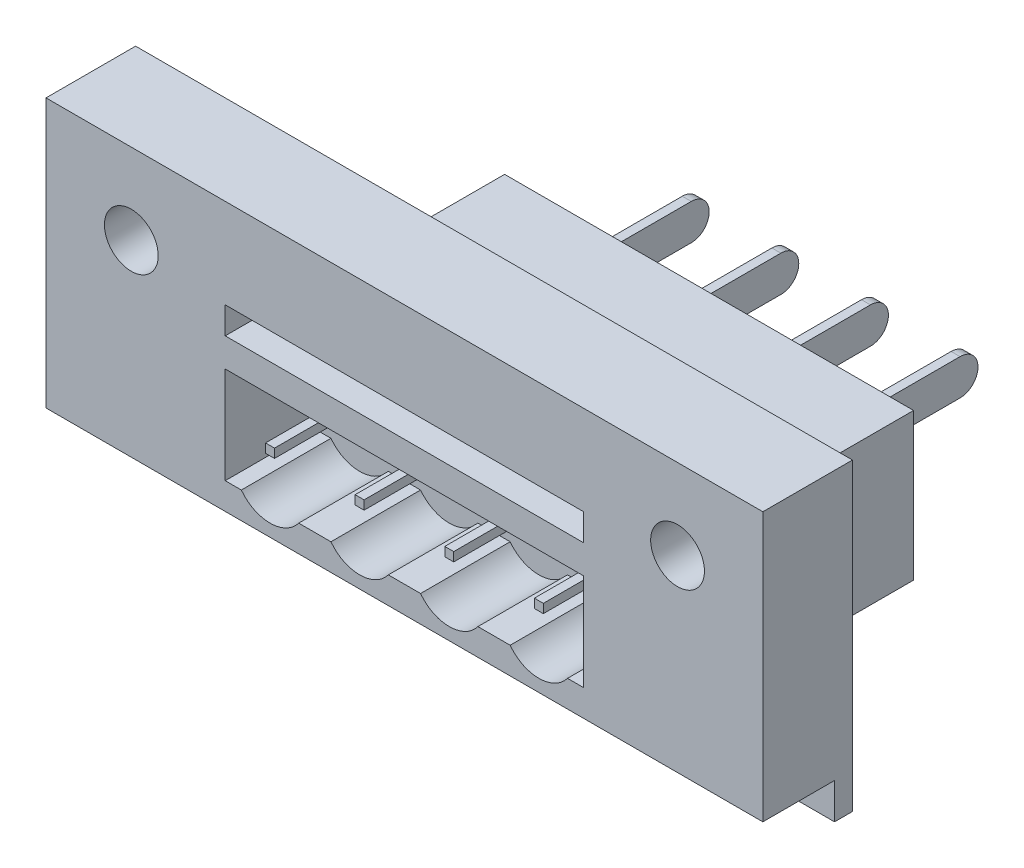
SolidWorks part; units mm, degrees
ref_plane "Front Plane" through (0, 0, 0) normal (0, 0, 1) x (1, 0, 0)
ref_plane "Top Plane" through (0, 0, 0) normal (0, 1, 0) x (1, 0, 0)
ref_plane "Right Plane" through (0, 0, 0) normal (1, 0, 0) x (0, 0, -1)
sketch "Sketch2" plane through (0, 0, 0) normal (0, 0, 1) x (1, 0, 0)
  line L0 (43.4756, 129.3243) -> (252.1422, 129.3243) construction
sketch "Sketch1" plane through (0, 0, 0) normal (0, 0, 1) x (1, 0, 0)
  line L0 (0, 7.493) -> (0, -7.493) construction
  line L1 (-20, 7.493) -> (20, 7.493)
  line L2 (-20, 7.493) -> (-20, -7.493)
  line L3 (-20, -7.493) -> (20, -7.493)
  line L4 (20, 7.493) -> (20, -7.493)
  line L5 (-20, 7.493) -> (20, -7.493) construction
  line L6 (-20, -7.493) -> (20, 7.493) construction
  line L7 (-11.41, -0.407) -> (11.41, -0.407)
  line L8 (-11.41, -0.407) -> (-11.41, -8.607)
  line L9 (-11.41, -8.607) -> (11.41, -8.607)
  line L10 (11.41, -8.607) -> (11.41, -0.407)
  line L11 (-15.24, 2.993) -> (15.24, 2.993) construction
  line L12 (-20, -7.493) -> (-20, -9.493)
  line L13 (-20, -9.493) -> (20, -9.493)
  line L14 (20, -9.493) -> (20, -7.493)
  line L15 (-5, -0.607) -> (-10, -0.607)
  line L16 (-10, 2.493) -> (10, 2.493)
  line L17 (-10, 2.493) -> (-10, 0.993)
  line L18 (-10, 0.993) -> (10, 0.993)
  line L19 (10, 2.493) -> (10, 0.993)
  line L20 (-10, -0.607) -> (-10, -6.007)
  line L21 (-10, -6.007) -> (-9.1, -6.007)
  line L22 (-5.9, -6.007) -> (-5, -6.007)
  line L23 (-5, -6.007) -> (-5, -0.607) construction
  line L24 (-12.5, -3.743) -> (12.5, -3.743) construction
  line L25 (-5, -0.607) -> (-5, -6.007)
  circle A0 centre (-15.24, 2.993) radius 1.5
  circle A1 centre (15.24, 2.993) radius 1.5
  arc A2 (-9.1, -6.007) -> (-5.9, -6.007) centre (-7.5, -4.807) ccw
  point P0 (0, 0)
  point P11 (0, -0.407)
  point P16 (0, 2.993)
  point P24 (0, 2.493)
  point P32 (-7.5, -6.807)
  point P37 (0, -3.743)
  dimension "D11" = 3
  dimension "D15" = 2
  dimension "D2" = 14.986
  dimension "D4" = 8.2
  dimension "D6" = 2
  dimension "D7" = 3.4
  dimension "D9" = 1.5
  dimension "D10" = 5
  dimension "D12" = 5
  dimension "D13" = 5.4
  dimension "D14" = 6.2
  dimension "D16" = 1.6
  dimension "D18" = 5.75
  dimension "D19" = 4.5
  dimension "D20" = 10
extrude "Boss-Extrude1" add sketch "Sketch1" along normal blind 5 contours L10 L3 L4 L1 L2 L8 L7 A1 A0 L16 L19 L18 L17 | L3 L10 L7 L8 A2 L21 L20 L15 L25 L22 | L21 A2 L22 L25 L15 L20 region at (0, 7.0658, 0) region at (1.6245, -4.0485, 0) region at (-7.5, -3.4951, 0)
extrude "Boss-Extrude2" add sketch "Sketch1<3>" along normal blind 1 contours L13 L14 L3 L10 L9 L8 L12 | L9 L10 L3 L8 region at (0, -8.6993, 0) region at (0, -8.05, 0)
sketch "Sketch1<3>" plane through (0, 0, 0) normal (0, 0, 1) x (1, 0, 0) same geometry as "Sketch1"
extrude "Cut-Extrude1" cut sketch "Sketch1<4>" along normal through all contours L21 A2 L22 L25 L15 L20 region at (-7.5, -3.4951, 0)
sketch "Sketch1<4>" plane through (0, 0, 0) normal (0, 0, 1) x (1, 0, 0) same geometry as "Sketch1"
pattern_linear "LPattern1" count 4 spacing 5 along (1, 0, 0) of "Cut-Extrude1"
extrude "Boss-Extrude3" add sketch "Sketch1<5>" against normal blind 12 contours L3 L10 L7 L8 A2 L21 L20 L15 L25 L22 | L21 A2 L22 L25 L15 L20 | L9 L10 L3 L8 region at (1.6245, -4.0485, 0) region at (0, -8.05, 0) region at (-7.5, -3.4951, 0)
sketch "Sketch1<5>" plane through (0, 0, 0) normal (0, 0, 1) x (1, 0, 0) same geometry as "Sketch1"
sketch "Sketch4" plane through (0, 0, 0) normal (0, 0, 1) x (1, 0, 0)
  line L1 (-7.75, -3.557) -> (-7.25, -3.557)
  line L2 (-7.75, -3.557) -> (-7.75, -3.057)
  line L3 (-7.75, -3.057) -> (-7.25, -3.057)
  line L4 (-7.25, -3.557) -> (-7.25, -3.057)
  line L5 (-7.75, -3.557) -> (-7.25, -3.057) construction
  line L6 (-7.75, -3.057) -> (-7.25, -3.557) construction
  line L8 (-10, -0.607) -> (-10, -6.007) construction
  point P0 (-7.5, -3.307)
  point P11 (-10, -3.307)
  dimension "D1" = 0.5
  dimension "D2" = 2.5
extrude "Boss-Extrude4" add sketch "Sketch4" along normal up to surface (5 mm away) up to face at (0, 0, 5)
sketch "Sketch5" plane through (0, 0, -12) normal (0, 0, -1) x (-1, 0, 0)
  line L0 (11.41, -0.407) -> (11.41, -8.607) construction
  line L1 (7.995, -3.507) -> (8.495, -3.507)
  line L2 (7.995, -3.507) -> (7.995, -5.507)
  line L3 (7.995, -5.507) -> (8.495, -5.507)
  line L4 (8.495, -3.507) -> (8.495, -5.507)
  line L5 (7.995, -3.507) -> (8.495, -5.507) construction
  line L6 (7.995, -5.507) -> (8.495, -3.507) construction
  line L7 (11.41, -8.607) -> (5.08, -8.607) construction
  point P0 (8.245, -4.507)
  point P5 (8.245, -8.607)
  point P13 (11.41, -4.507)
  dimension "D1" = 2
  dimension "D2" = 0.5
  dimension "D3" = 6.33
extrude "Boss-Extrude5" add sketch "Sketch5" along normal blind 8
fillet "Fillet1" radius 1 2 edges at (-8.245, -5.507, -20) (-8.245, -3.507, -20)
pattern_linear "LPattern2" count 4 spacing 5 along (1, 0, 0) of "Boss-Extrude4", "Boss-Extrude5", "Fillet1"
equation "\"P\" = 4'Number of pins"
equation "\"D1@Sketch1\"=\"P\"*5mm+20mm"
equation "\"D3@Sketch1\"=\"P\"*5.08mm+2.5mm"
equation "\"D5@Sketch1\"=(\"P\"-1)*5.08mm+15.24mm"
equation "\"D8@Sketch1\"=5mm*\"P\""
equation "\"D17@Sketch1\"=5mm*\"P\"+5mm"
equation "\"D1@LPattern1\"=\"P\""
equation "\"D1@LPattern2\"=\"P\""
